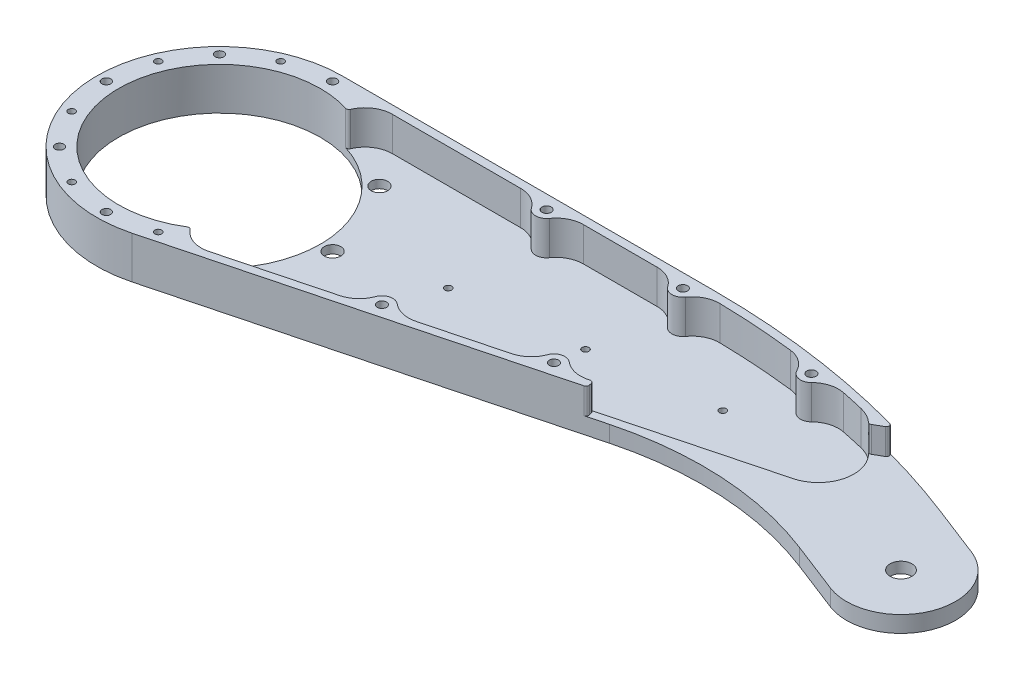
SolidWorks part; units mm, degrees
ref_plane "Спереди" through (0, 0, 0) normal (0, 0, 1) x (1, 0, 0)
ref_plane "Сверху" through (0, 0, 0) normal (0, 1, 0) x (1, 0, 0)
ref_plane "Справа" through (0, 0, 0) normal (1, 0, 0) x (0, 0, -1)
ref_plane "Плоскость4" through (0, 6, 0) normal (0, 1, 0) x (1, 0, 0)
sketch "Эскиз1" plane through (0, 6, 0) normal (0, 1, 0) x (1, 0, 0)
  line L0 (11.3988, -43.5324) -> (187.8755, 2.6774)
  line L1 (187.8755, 2.6774) -> (242.7579, -18.6427)
  line L2 (257.2421, 18.6427) -> (238.5994, 25.8849)
  line L3 (136.6047, 45) -> (0, 45)
  arc A0 (0, 45) -> (11.3988, -43.5324) centre (0, 0) ccw
  arc A1 (242.7579, -18.6427) -> (257.2421, 18.6427) centre (250, 0) ccw
  arc A2 (238.5994, 25.8849) -> (136.6047, 45) centre (136.6047, -236.6697) ccw
extrude "Бобышка-Вытянуть1" add sketch "Эскиз1" against normal blind 6
sketch "Эскиз2" plane through (0, 6, 0) normal (0, 1, 0) x (-1, 0, 0)
  line L0 (-118.5109, -42) -> (-21.4068, -42)
  line L1 (-31.3475, 35.2077) -> (-143.0826, 5.9503)
  line L2 (-143.0826, 5.9503) -> (-143.8426, 8.8524)
  line L3 (-143.8426, 8.8524) -> (-11.3988, 43.5324)
  line L4 (0, -45) -> (-136.6047, -45)
  line L5 (-211.069, -33.2121) -> (-207.1483, -30.9537)
  arc A0 (-21.4068, -42) -> (-11.8803, -35.0408) centre (-21.4068, -32) ccw
  arc A1 (-11.8803, -35.0408) -> (-20.3689, 30.8886) centre (0, 0) cw
  arc A2 (-20.3689, 30.8886) -> (-31.3475, 35.2077) centre (-28.8144, 25.5339) ccw
  arc A3 (-11.3988, 43.5324) -> (0, -45) centre (0, 0) cw
  arc A4 (-136.6047, -45) -> (-210.8334, -35.0433) centre (-136.6047, 236.6697) cw
  arc A5 (-210.8334, -35.0433) -> (-211.069, -33.2121) centre (-210.5698, -34.0786) cw
  arc A6 (-207.1483, -30.9537) -> (-200.8795, -34.4863) centre (-197.8811, -21.8368) ccw
  arc A7 (-200.8795, -34.4863) -> (-141.6391, -41.9545) centre (-136.6047, 236.6697) ccw
  arc A8 (-141.6391, -41.9545) -> (-133.2738, -37.7018) centre (-141.4585, -31.9562) ccw
  arc A9 (-133.2738, -37.7018) -> (-126.7174, -37.7143) centre (-130, -40) cw
  arc A10 (-126.7174, -37.7143) -> (-118.5109, -42) centre (-118.5109, -32) ccw
extrude "Бобышка-Вытянуть2" add sketch "Эскиз2" along normal blind 9.5
sketch "Эскиз3" plane through (0, 6, 0) normal (0, 1, 0) x (-1, 0, 0)
  line L0 (-118.5109, -42) -> (-21.4068, -42)
  line L1 (-31.3475, 35.2077) -> (-201.1741, -9.2608)
  arc A0 (-21.4068, -42) -> (-11.8803, -35.0408) centre (-21.4068, -32) ccw
  arc A1 (-11.8803, -35.0408) -> (-20.3689, 30.8886) centre (0, 0) cw
  arc A2 (-20.3689, 30.8886) -> (-31.3475, 35.2077) centre (-28.8144, 25.5339) ccw
  arc A3 (-201.1741, -9.2608) -> (-200.8795, -34.4863) centre (-197.8811, -21.8368) ccw
  arc A4 (-200.8795, -34.4863) -> (-141.6391, -41.9545) centre (-136.6047, 236.6697) ccw
  arc A5 (-141.6391, -41.9545) -> (-133.2738, -37.7018) centre (-141.4585, -31.9562) ccw
  arc A6 (-133.2738, -37.7018) -> (-126.7174, -37.7143) centre (-130, -40) cw
  arc A7 (-126.7174, -37.7143) -> (-118.5109, -42) centre (-118.5109, -32) ccw
extrude "Вырез-Вытянуть1" cut sketch "Эскиз3" against normal blind 3
sketch "Эскиз4" plane through (0, 3, 0) normal (0, 1, 0) x (-1, 0, 0)
  line L0 (-68.5109, -42) -> (-91.4891, -42)
  arc A0 (-83.2826, -37.7143) -> (-76.7174, -37.7143) centre (-80, -40) cw
  arc A1 (-76.7174, -37.7143) -> (-68.5109, -42) centre (-68.5109, -32) ccw
  arc A2 (-91.4891, -42) -> (-83.2826, -37.7143) centre (-91.4891, -32) ccw
extrude "Бобышка-Вытянуть3" add sketch "Эскиз4" along normal blind 12.5
sketch "Эскиз5" plane through (0, 3, 0) normal (0, 1, 0) x (-1, 0, 0)
  arc A0 (-183.4802, -33.6307) -> (-177.0946, -34.6607) centre (-180.6622, -36.4696) cw
  arc A1 (-177.0946, -34.6607) -> (-169.3505, -40.0694) centre (-168.1755, -30.1387) ccw
  arc A2 (-169.3505, -40.0694) -> (-192.5321, -36.3302) centre (-136.6047, 236.6697) cw
  arc A3 (-192.5321, -36.3302) -> (-183.4802, -33.6307) centre (-190.5252, -26.5336) ccw
extrude "Бобышка-Вытянуть4" add sketch "Эскиз5" along normal blind 12.5
sketch "Эскиз6" plane through (0, 3, 0) normal (0, 1, 0) x (-1, 0, 0)
  line L0 (-141.621, 6.333) -> (-119.3922, 12.1535)
  arc A0 (-126.2455, 5.9288) -> (-132.5966, 4.2658) centre (-130, 7.3085) cw
  arc A1 (-132.5966, 4.2658) -> (-141.621, 6.333) centre (-139.088, -3.3409) ccw
  arc A2 (-119.3922, 12.1535) -> (-126.2455, 5.9288) centre (-116.8591, 2.4797) ccw
extrude "Бобышка-Вытянуть5" add sketch "Эскиз6" along normal blind 12.5
sketch "Эскиз7" plane through (0, 3, 0) normal (0, 1, 0) x (-1, 0, 0)
  line L0 (-91.621, 19.4253) -> (-69.3922, 25.2459)
  arc A0 (-76.2455, 19.0212) -> (-82.5966, 17.3581) centre (-80, 20.4008) cw
  arc A1 (-82.5966, 17.3581) -> (-91.621, 19.4253) centre (-89.088, 9.7515) ccw
  arc A2 (-69.3922, 25.2459) -> (-76.2455, 19.0212) centre (-66.8591, 15.572) ccw
extrude "Бобышка-Вытянуть6" add sketch "Эскиз7" along normal blind 12.5
sketch "Эскиз8" plane through (0, 0, 0) normal (0, 0, 1) x (1, 0, 0)
  line L0 (37, 15.5) -> (0, 15.5)
  line L1 (0, 15.5) -> (0, 0)
  line L2 (0, 0) -> (37, 0)
  line L3 (37, 0) -> (37, 15.5)
  line L4 (0, 15.5) -> (0, 0) construction
revolve "Вырез-Повернуть1" cut sketch "Эскиз8" angle 360 about L4 reverse direction yes
hole_wizard "Диаметр отверстия Ø2.5 (2.5)1" positions "Эскиз10" profile "Эскиз9" hole size "Ø2.5" standard "Ansi Metric"
sketch "Эскиз10" plane through (0, 0, 0) normal (0, -1, 0) x (-1, 0, 0)
  point P0 (38.341, 15.8814)
  point P1 (38.341, -15.8814)
  point P2 (15.8814, -38.341)
  point P3 (-15.8814, -38.341)
  point P4 (15.8814, 38.341)
sketch "Эскиз9" plane through (-38.341, 0, -15.8814) normal (1, 0, 0) x (0, 0, -1)
  line L0 (0, 0) -> (0, 15.5)
  line L1 (0, 15.5) -> (1.25, 15.5)
  line L2 (1.25, 15.5) -> (1.25, 0)
  line L5 (1.25, 0) -> (0, 0)
  line L11 (0, -6.35) -> (0, 107.95) construction
  dimension "Диаметр сквозного отверстия" = 2.5
  dimension "Глубина сквозного отверстия" = 15.5
hole_wizard "Диаметр отверстия Ø2.5 (2.5)2" positions "Эскиз12" profile "Эскиз11" hole size "Ø2.5" standard "Ansi Metric"
sketch "Эскиз12" plane through (0, 0, 0) normal (0, -1, 0) x (-1, 0, 0)
  point P0 (-163.6626, 20.9657)
  point P1 (-119.0273, 15.2478)
  point P2 (-74.3921, 9.5298)
sketch "Эскиз11" plane through (163.6626, 0, -20.9657) normal (1, 0, 0) x (0, 0, -1)
  line L0 (0, 0) -> (0, 15.5)
  line L1 (0, 15.5) -> (1.25, 15.5)
  line L2 (1.25, 15.5) -> (1.25, 0)
  line L5 (1.25, 0) -> (0, 0)
  line L11 (0, -6.35) -> (0, 107.95) construction
  dimension "Диаметр сквозного отверстия" = 2.5
  dimension "Глубина сквозного отверстия" = 15.5
hole_wizard "Цековка для винта с заклепочной головкой M31" positions "Эскиз14" profile "Эскиз13" counterbore size "M3" standard "Ansi Metric"
sketch "Эскиз14" plane through (0, 0, 0) normal (0, -1, 0) x (-1, 0, 0)
  point P0 (-130, 40)
  point P1 (-80, 40)
  point P2 (-80, -20.4008)
  point P3 (-130, -7.3085)
  point P4 (-180.6622, 36.4696)
sketch "Эскиз13" plane through (130, 0, -40) normal (1, 0, 0) x (0, 0, -1)
  line L0 (0, 0) -> (0, 15.5)
  line L1 (0, 15.5) -> (1.7, 15.5)
  line L3 (1.7, 15.5) -> (1.7, 3)
  line L4 (1.7, 3) -> (3.025, 3)
  line L5 (3.025, 3) -> (3.025, 0)
  line L7 (3.025, 0) -> (0, 0)
  line L11 (0, -6.35) -> (0, 107.95) construction
  dimension "Диаметр сквозного отверстия" = 3.4
  dimension "Глубина сквозного отверстия" = 15.5
  dimension "Диаметр цековки" = 6.05
  dimension "Глубина цековки" = 3
hole_wizard "Цековка для винта с заклепочной головкой M32" positions "Эскиз16" profile "Эскиз15" counterbore size "M3" standard "Ansi Metric"
sketch "Эскиз16" plane through (0, 0, 0) normal (0, -1, 0) x (-1, 0, 0)
  point P0 (29.3449, 29.3449)
  point P1 (0, 41.5)
  point P2 (0, -41.5)
  point P3 (29.3449, -29.3449)
  point P4 (41.5, 0)
sketch "Эскиз15" plane through (-29.3449, 0, -29.3449) normal (1, 0, 0) x (0, 0, -1)
  line L0 (0, 0) -> (0, 15.5)
  line L1 (0, 15.5) -> (1.6, 15.5)
  line L3 (1.6, 15.5) -> (1.6, 3)
  line L4 (1.6, 3) -> (3.025, 3)
  line L5 (3.025, 3) -> (3.025, 0)
  line L7 (3.025, 0) -> (0, 0)
  line L11 (0, -6.35) -> (0, 107.95) construction
  dimension "Диаметр сквозного отверстия" = 3.2
  dimension "Глубина сквозного отверстия" = 15.5
  dimension "Диаметр цековки" = 6.05
  dimension "Глубина цековки" = 3
hole_wizard "Отверстие1" positions "Эскиз18" profile "Эскиз17" legacy
sketch "Эскиз18" plane through (0, 3, 0) normal (0, 1, 0) x (1, 0, 0)
  point P0 (29.3449, -29.3449)
  point P1 (29.3449, 29.3449)
  point P2 (41.5, 0)
sketch "Эскиз17" plane through (29.3449, 3, 29.3449) normal (1, 0, 0) x (0, 0, 1)
  line L0 (0, 0) -> (0, 3)
  line L1 (0, 3) -> (3.025, 3)
  line L2 (3.025, 3) -> (3.025, 0)
  line L3 (3.025, 0) -> (0, 0)
  line L4 (0, 110) -> (0, -10) construction
  dimension "Диаметр" = 6.05
  dimension "Глубина" = 3
hole_wizard "Отверстие обработанное метчиком M14x1.51" positions "Эскиз20" profile "Эскиз19" tap size "M14x1.5" standard "Ansi Metric"
sketch "Эскиз20" plane through (0, 0, 0) normal (0, -1, 0) x (-1, 0, 0)
  point P0 (-250, 0)
sketch "Эскиз19" plane through (250, 0, 0) normal (1, 0, 0) x (0, 0, -1)
  line L0 (0, 0) -> (0, 15.5)
  line L1 (0, 15.5) -> (4, 15.5)
  line L3 (4, 15.5) -> (4, 2)
  line L4 (4, 2) -> (7, 2)
  line L5 (7, 2) -> (7, 0)
  line L7 (7, 0) -> (0, 0)
  line L11 (0, -6.35) -> (0, 107.95) construction
  dimension "Диаметр проходного сверла" = 8
  dimension "Глубина проходного сверла" = 15.5
  dimension "Диаметр резьбы" = 14
  dimension "Глубина резьбы" = 2
fillet "Скругление1" radius 1 5 edges at (143.8426, 10.75, 8.8524) (11.8803, 9.25, -35.0408) (207.1483, 10.75, -30.9537) (20.3689, 9.25, 30.8886) (143.0826, 10.75, 5.9503) tangent propagation no
fillet "Скругление2" radius 120 1 edges at (187.8755, 3, -2.6774) tangent propagation no
